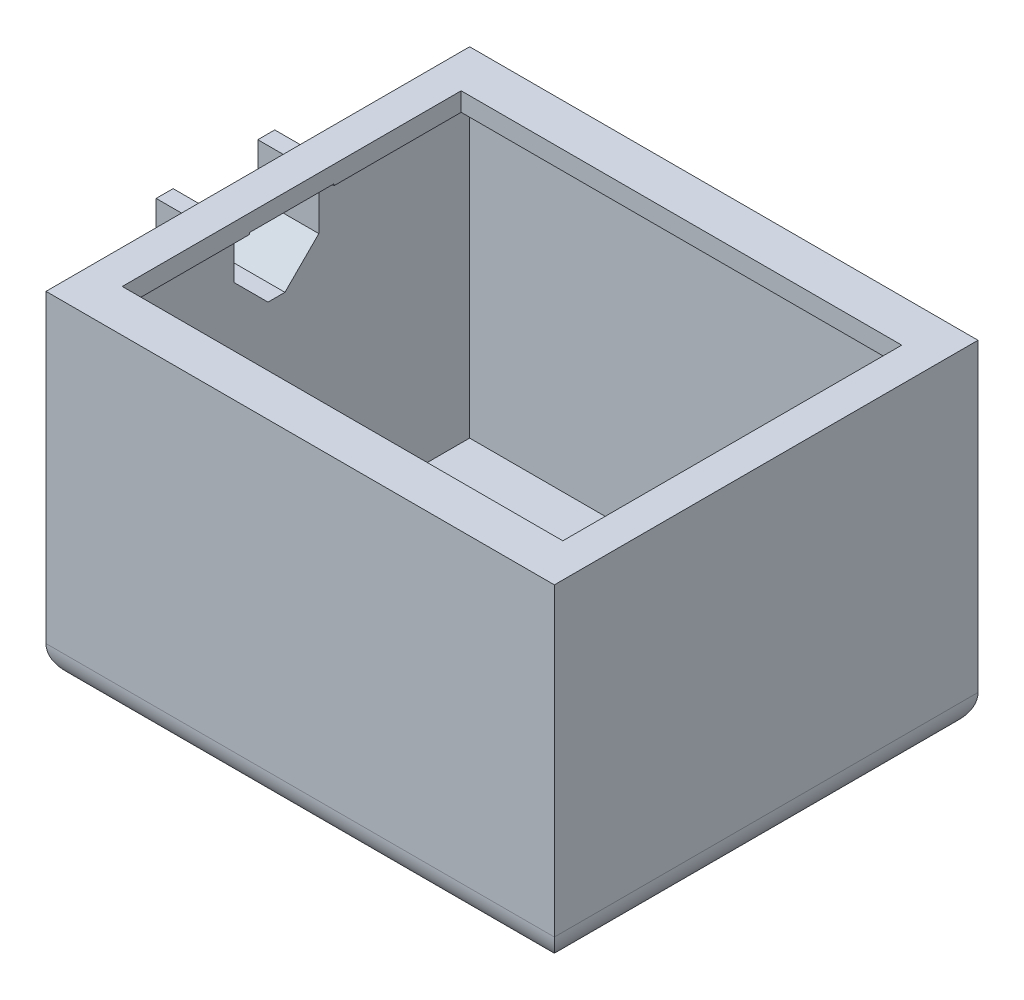
SolidWorks part; units mm, degrees
ref_plane "Front Plane" through (0, 0, 0) normal (0, 0, 1) x (1, 0, 0)
ref_plane "Top Plane" through (0, 0, 0) normal (0, 1, 0) x (1, 0, 0)
ref_plane "Right Plane" through (0, 0, 0) normal (1, 0, 0) x (0, 0, -1)
sketch "Sketch1" plane through (0, 0, 0) normal (0, 1, 0) x (1, 0, 0)
  line L1 (-30, 25) -> (30, 25)
  line L2 (-30, 25) -> (-30, -25)
  line L3 (-30, -25) -> (30, -25)
  line L4 (30, 25) -> (30, -25)
  line L5 (-30, 25) -> (30, -25) construction
  line L6 (-30, -25) -> (30, 25) construction
  point P0 (0, 0)
  dimension "D1" = 60
  dimension "D2" = 50
extrude "Boss-Extrude1" add sketch "Sketch1" along normal blind 40
shell "Shell1" thickness 2.2
sketch "Sketch2" plane through (0, 40, 0) normal (0, 1, 0) x (1, 0, 0)
  line L1 (-26, 20) -> (26, 20)
  line L2 (-26, 20) -> (-26, -20)
  line L3 (-26, -20) -> (26, -20)
  line L4 (26, 20) -> (26, -20)
  line L5 (-26, 20) -> (26, -20) construction
  line L6 (-26, -20) -> (26, 20) construction
  point P0 (0, 0)
  dimension "D1" = 52
  dimension "D2" = 40
extrude "Cut-Extrude1" cut sketch "Sketch2" against normal blind 10
sketch "Sketch3" plane through (-30, 0, 0) normal (1, 0, 0) x (0, 0, -1)
  line L0 (-25, 40) -> (-25, 0) construction
  line L1 (5, 38) -> (-5, 38)
  line L2 (5, 38) -> (5, 28)
  line L3 (5, 28) -> (-5, 28)
  line L4 (-5, 38) -> (-5, 28)
  line L5 (5, 38) -> (-5, 28) construction
  line L6 (5, 28) -> (-5, 38) construction
  line L7 (25, 40) -> (-25, 40) construction
  point P0 (0, 33)
  dimension "D1" = 10
  dimension "D2" = 10
  dimension "D3" = 20
  dimension "D4" = 2
extrude "Cut-Extrude2" cut sketch "Sketch3" along normal blind 5
sketch "Sketch4" plane through (-30, 0, 0) normal (1, 0, 0) x (0, 0, -1)
  line L0 (-5, 38) -> (-7, 38)
  line L1 (-7, 38) -> (-7, 26)
  line L2 (-7, 26) -> (7, 26)
  line L3 (7, 26) -> (7, 38)
  line L4 (7, 38) -> (5, 38)
  line L5 (5, 38) -> (5, 28)
  line L6 (5, 28) -> (-5, 28)
  line L7 (-5, 28) -> (-5, 38)
  dimension "D1" = 14
  dimension "D2" = 12
extrude "Boss-Extrude2" add sketch "Sketch4" against normal blind 5
chamfer "Chamfer3" distance 5 angle 45 1 edges at (-30, 26, 0)
chamfer "Chamfer4" distance 4 angle 45 2 edges at (-31.4, 28, -5) (-31.4, 28, 5)
fillet "Fillet1" radius 4 4 edges at (0, 0, -25) (30, 0, 0) (-30, 0, 0) (0, 0, 25)
